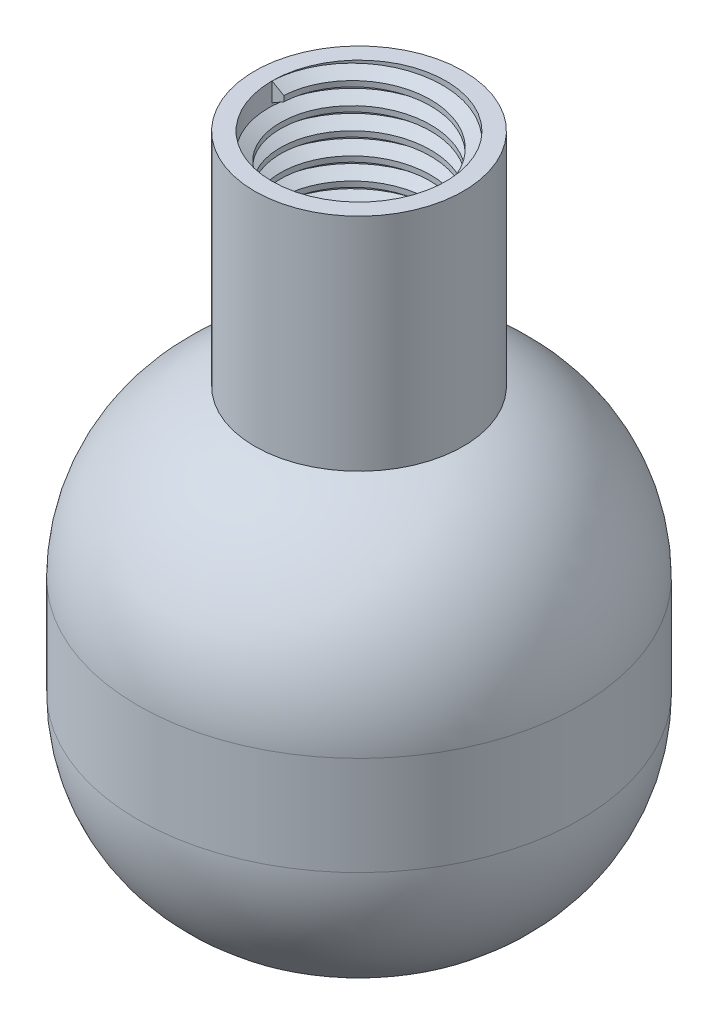
SolidWorks part; units mm, degrees
ref_plane "Front Plane" through (0, 0, 0) normal (0, 0, 1) x (1, 0, 0)
ref_plane "Top Plane" through (0, 0, 0) normal (0, 1, 0) x (1, 0, 0)
ref_plane "Right Plane" through (0, 0, 0) normal (1, 0, 0) x (0, 0, -1)
sketch "Sketch1" plane through (0, 0, 0) normal (0, 1, 0) x (1, 0, 0)
  circle A0 centre (0, 0) radius 5.9944
  dimension "D1" = 11.9888
extrude "Boss-Extrude1" add sketch "Sketch1" along normal blind 12.7
sketch "Sketch2" plane through (0, 12.7, 0) normal (0, 1, 0) x (1, 0, 0)
  circle A0 centre (0, 0) radius 5
  dimension "D1" = 10
extrude "Cut-Extrude1" cut sketch "Sketch2" against normal through all
thread "Thread1" pitch 1.25 method extrude profile "Thread Profile1" start angle 0, offset 0, length 10, pitch 1.25, diameter 10
ref_plane "Plane1" through (-5, 12.7, 0) normal (0, 0, 1) x (-1, 0, 0)
sketch "Thread Profile1" plane through (-5, 12.7, 0) normal (0, 0, 1) x (-1, 0, 0)
  line L0 (0, 0) -> (0, 1.25) construction
  line L11 (0, 0) -> (0, 1.0937)
  line L12 (0, 1.0937) -> (-0.6766, 0.7031)
  line L13 (-0.6766, 0.7031) -> (-0.6766, 0.3906)
  line L15 (-0.6766, 0.3906) -> (0, 0)
  line L17 (-0.6766, 0.5469) -> (0, 0.5469) construction
  point P2 (0, 0)
  dimension "Pitch" = 1.25
  dimension "Profile_Angle" = 60
  dimension "Profile_Land" = 0.3125
  dimension "Profile_Height" = 0.6766
sketch "Sketch6" plane through (0, 0, 0) normal (0, -1, 0) x (1, 0, 0)
  circle A0 centre (0, 0) radius 12.7
  dimension "D1" = 25.4
extrude "Boss-Extrude2" add sketch "Sketch6" along normal blind 25.4
fillet "Fillet1" radius 10.16 2 edges at (0, -25.4, -12.7) (0, 0, -12.7)
